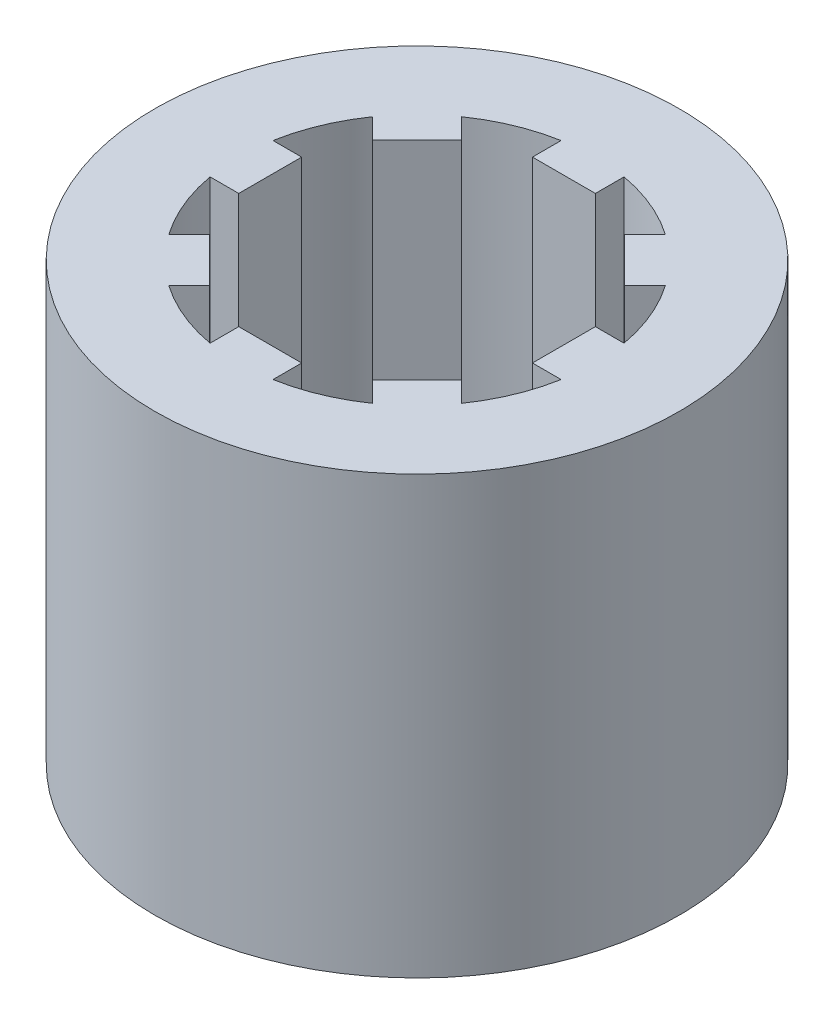
SolidWorks part; units mm, degrees
ref_plane "Front Plane" through (0, 0, 0) normal (0, 0, 1) x (1, 0, 0)
ref_plane "Top Plane" through (0, 0, 0) normal (0, 1, 0) x (1, 0, 0)
ref_plane "Right Plane" through (0, 0, 0) normal (1, 0, 0) x (0, 0, -1)
sketch "Sketch3" plane through (0, 0, 0) normal (0, 1, 0) x (1, 0, 0)
  line L2 (2.3813, 13.282) -> (2.3813, 11.1125)
  line L3 (2.3813, 11.1125) -> (-2.3813, 11.1125)
  line L4 (-2.3812, 13.282) -> (-2.3813, 11.1125)
  line L5 (2.3812, 15.875) -> (-2.3813, 11.1125) construction
  line L6 (2.3813, 11.1125) -> (-2.3813, 15.875) construction
  line L7 (11.0756, 7.708) -> (9.5415, 6.1739)
  line L8 (9.5415, 6.1739) -> (6.1739, 9.5415)
  line L9 (7.708, 11.0756) -> (6.1739, 9.5415)
  line L11 (13.282, -2.3813) -> (11.1125, -2.3813)
  line L12 (11.1125, -2.3813) -> (11.1125, 2.3813)
  line L13 (13.282, 2.3813) -> (11.1125, 2.3813)
  line L15 (7.708, -11.0756) -> (6.1739, -9.5415)
  line L16 (6.1739, -9.5415) -> (9.5415, -6.1739)
  line L17 (11.0756, -7.708) -> (9.5415, -6.1739)
  line L19 (-2.3813, -13.282) -> (-2.3813, -11.1125)
  line L20 (-2.3813, -11.1125) -> (2.3813, -11.1125)
  line L21 (2.3813, -13.282) -> (2.3813, -11.1125)
  line L23 (-11.0756, -7.708) -> (-9.5415, -6.1739)
  line L24 (-9.5415, -6.1739) -> (-6.1739, -9.5415)
  line L25 (-7.708, -11.0756) -> (-6.1739, -9.5415)
  line L27 (-13.282, 2.3812) -> (-11.1125, 2.3812)
  line L28 (-11.1125, 2.3812) -> (-11.1125, -2.3813)
  line L29 (-13.282, -2.3813) -> (-11.1125, -2.3813)
  line L31 (-7.708, 11.0756) -> (-6.1739, 9.5415)
  line L32 (-6.1739, 9.5415) -> (-9.5415, 6.1739)
  line L33 (-11.0756, 7.708) -> (-9.5415, 6.1739)
  line L41 (0, 0) -> (0, 20.8399) construction
  line L42 (-2.3813, 15.875) -> (-2.3812, 13.282) construction
  line L43 (-2.3813, 15.875) -> (2.3812, 15.875) construction
  line L44 (2.3812, 15.875) -> (2.3813, 13.282) construction
  line L45 (0, 0) -> (25.1483, 0) construction
  line L46 (0, 0) -> (0, -21.283) construction
  circle A0 centre (0, 0) radius 19.8438
  arc A1 (-13.282, -2.3813) -> (-11.0756, -7.708) centre (0, 0) ccw
  arc A2 (-11.0756, 7.708) -> (-13.282, 2.3812) centre (0, 0) ccw
  arc A3 (-2.3812, 13.282) -> (-7.708, 11.0756) centre (0, 0) ccw
  arc A4 (7.708, 11.0756) -> (2.3813, 13.282) centre (0, 0) ccw
  arc A5 (13.282, 2.3813) -> (11.0756, 7.708) centre (0, 0) ccw
  arc A6 (11.0756, -7.708) -> (13.282, -2.3813) centre (0, 0) ccw
  arc A7 (2.3813, -13.282) -> (7.708, -11.0756) centre (0, 0) ccw
  arc A8 (-7.708, -11.0756) -> (-2.3813, -13.282) centre (0, 0) ccw
  point P4 (0, 13.4937)
  point P16 (11.1125, 0)
  point P22 (0, -11.1125)
  point P39 (0, 0)
  dimension "D1" = 26.9875
  dimension "D2" = 6.35
  dimension "D3" = 4.7625
  dimension "D5" = 4.7625
  dimension "D4" = 8
extrude "Boss-Extrude2" add sketch "Sketch3" along normal blind 33.02
